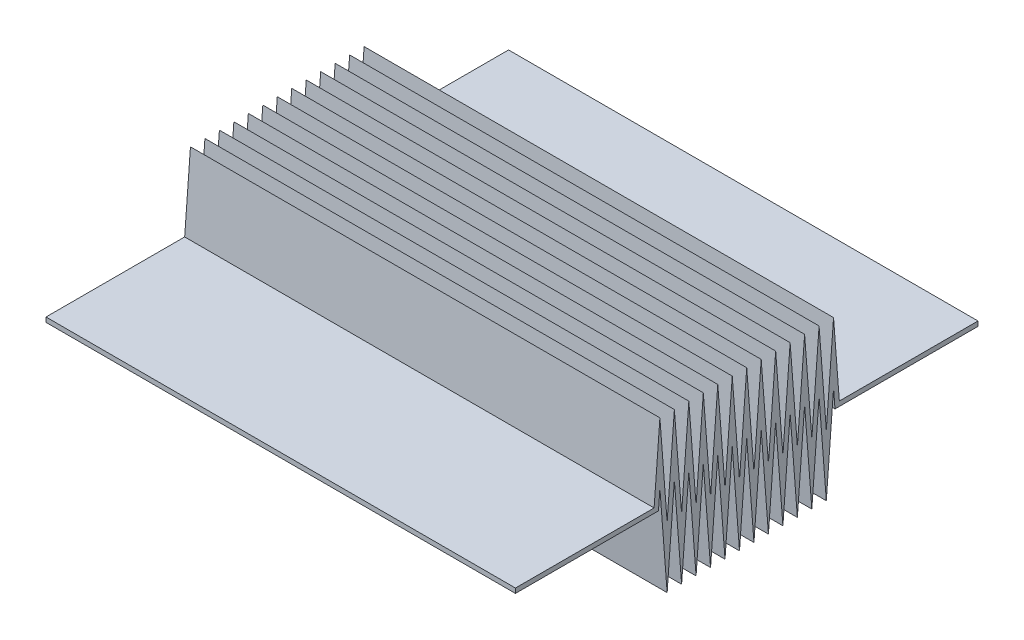
SolidWorks part; units mm, degrees
ref_plane "Front Plane" through (0, 0, 0) normal (0, 0, 1) x (1, 0, 0)
ref_plane "Top Plane" through (0, 0, 0) normal (0, 1, 0) x (1, 0, 0)
ref_plane "Right Plane" through (0, 0, 0) normal (1, 0, 0) x (0, 0, -1)
sketch "Sketch2" plane through (0, 0, 0) normal (0, 0, 1) x (1, 0, 0)
  line L1 (-27.5, 10) -> (27.5, 10)
  line L2 (-27.5, 10) -> (-27.5, 0)
  line L3 (-27.5, 0) -> (27.5, 0)
  line L4 (27.5, 10) -> (27.5, 0)
  point P4 (0, 0)
  dimension "D1" = 10
  dimension "D2" = 55
sketch "Sketch3" plane through (0, 0, 0) normal (1, 0, 0) x (0, 0, -1)
  line L0 (0, 10) -> (49.266, 10) construction
  line L1 (0, 0) -> (49.266, 0) construction
  line L3 (15, 5) -> (15.3853, 10)
  line L4 (15.3853, 10) -> (16.156, 0)
  line L5 (16.156, 0) -> (16.9266, 10)
  line L6 (16.9266, 10) -> (17.6972, 0)
  line L7 (17.6972, 0) -> (18.4679, 10)
  line L8 (18.4679, 10) -> (19.2385, 0)
  line L9 (19.2385, 0) -> (20.0091, 10)
  line L10 (20.0091, 10) -> (20.7798, 0)
  line L11 (20.7798, 0) -> (21.5504, 10)
  line L12 (21.5504, 10) -> (22.3211, 0)
  line L13 (22.3211, 0) -> (23.0917, 10)
  line L14 (23.0917, 10) -> (23.8623, 0)
  line L15 (23.8623, 0) -> (24.633, 10)
  line L16 (24.633, 10) -> (25.4036, 0)
  line L17 (25.4036, 0) -> (26.1743, 10)
  line L18 (26.1743, 10) -> (26.9449, 0)
  line L19 (0, 10) -> (0, 0) construction
  line L20 (26.9449, 0) -> (27.7155, 10)
  line L21 (27.7155, 10) -> (28.4862, 0)
  line L22 (28.4862, 0) -> (29.2568, 10)
  line L23 (29.2568, 10) -> (30.0274, 0)
  line L24 (30.0274, 0) -> (30.7981, 10)
  line L25 (30.7981, 10) -> (31.5687, 0)
  line L26 (31.5687, 0) -> (32.3394, 10)
  line L27 (32.3394, 10) -> (33.11, 0)
  line L28 (33.11, 0) -> (33.8806, 10)
  line L29 (33.8806, 10) -> (34.266, 5)
  line L30 (49.266, 10) -> (49.266, 0) construction
  line L31 (15, 5) -> (0, 5)
  line L32 (34.266, 5) -> (49.266, 5)
  line L34 (49.266, 4.75) -> (49.266, 22.75) construction
  dimension "D2" = 15
  dimension "D1" = 10
  dimension "D3" = 15
extrude "Extrude-Thin1" add sketch "Sketch3" against normal mid plane 50 thin thin type mid plane wall 0.5
